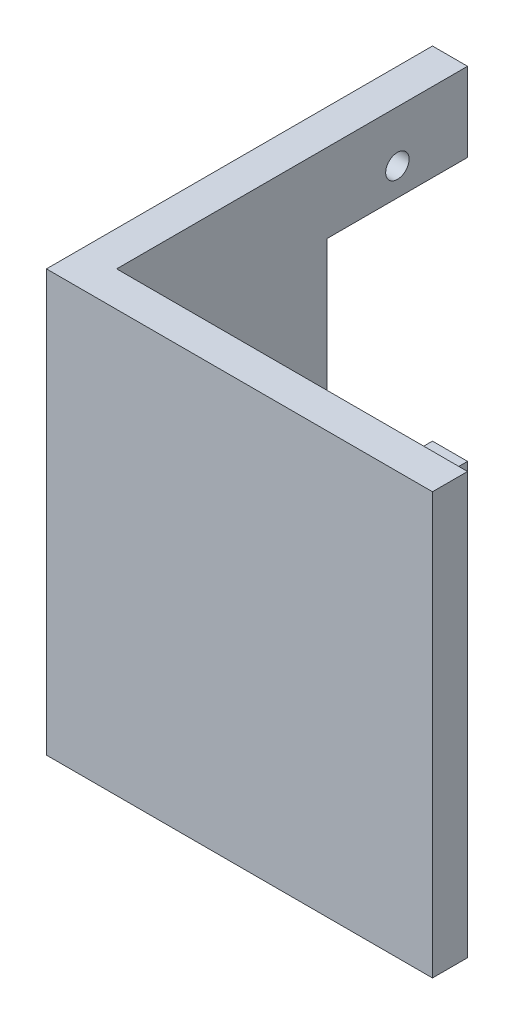
SolidWorks part; units mm, degrees
ref_plane "Front Plane" through (0, 0, 0) normal (0, 0, 1) x (1, 0, 0)
ref_plane "Top Plane" through (0, 0, 0) normal (0, 1, 0) x (1, 0, 0)
ref_plane "Right Plane" through (0, 0, 0) normal (1, 0, 0) x (0, 0, -1)
sketch "Sketch1" plane through (0, 0, 0) normal (0, 1, 0) x (1, 0, 0)
  line L0 (0, 30) -> (0, 0)
  line L1 (0, 0) -> (30, 0)
  point P2 (0, 0)
  dimension "D1" = 30
extrude "Extrude-Thin1" add sketch "Sketch1" along normal mid plane 36 thin thin type one direction wall 3
sketch "Sketch2" plane through (0, 0, 0) normal (1, 0, 0) x (0, 0, -1)
  line L0 (-4.3404, 0) -> (30.9328, 0) construction
  line L1 (30, 11.25) -> (18, 11.25)
  line L2 (30, 11.25) -> (30, -11.25)
  line L3 (30, -11.25) -> (18, -11.25)
  line L4 (18, 11.25) -> (18, -11.25)
  line L5 (30, 11.25) -> (18, -11.25) construction
  line L6 (30, -11.25) -> (18, 11.25) construction
  line L8 (30, 18) -> (30, -18) construction
  line L9 (24, 22.9117) -> (24, -24.2701) construction
  circle A0 centre (24, -13.625) radius 1
  circle A1 centre (24, 13.625) radius 1
  point P0 (24, 0)
  point P16 (23.8239, 22.9117)
  point P17 (0, 0)
  dimension "D3" = 2
  dimension "D1" = 22.5
  dimension "D2" = 12
  dimension "D4" = 27.25
extrude "Cut-Extrude1" cut sketch "Sketch2" against normal through all
